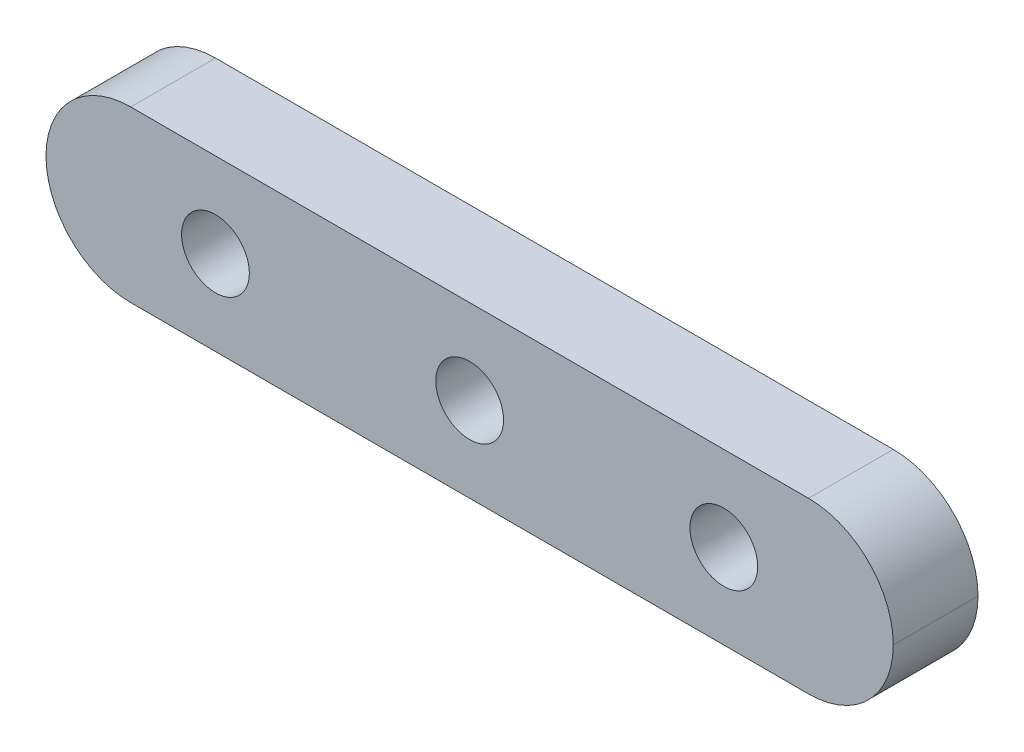
SolidWorks part; units mm, degrees
ref_plane "前视基准面" through (0, 0, 0) normal (0, 0, 1) x (1, 0, 0)
ref_plane "上视基准面" through (0, 0, 0) normal (0, 1, 0) x (1, 0, 0)
ref_plane "右视基准面" through (0, 0, 0) normal (1, 0, 0) x (0, 0, -1)
sketch "草图1" plane through (0, 0, 0) normal (0, 0, 1) x (1, 0, 0)
  line L0 (0, 5) -> (0, -5) construction
  line L1 (-25, 5) -> (25, 5)
  line L2 (-25, 5) -> (-25, -5)
  line L3 (-25, -5) -> (25, -5)
  line L4 (25, 5) -> (25, -5)
  line L5 (-25, 5) -> (25, -5) construction
  line L6 (-25, -5) -> (25, 5) construction
  circle A0 centre (-15, 0) radius 2
  circle A1 centre (15, 0) radius 2
  circle A2 centre (0, 0) radius 2
  point P0 (0, 0)
  dimension "D3" = 10
  dimension "D4" = 4
  dimension "D1" = 50
  dimension "D2" = 10
extrude "凸台-拉伸1" add sketch "草图1" along normal blind 5
fillet "圆角1" radius 5 4 edges at (25, -5, 2.5) (25, 5, 2.5) (-25, -5, 2.5) (-25, 5, 2.5)
